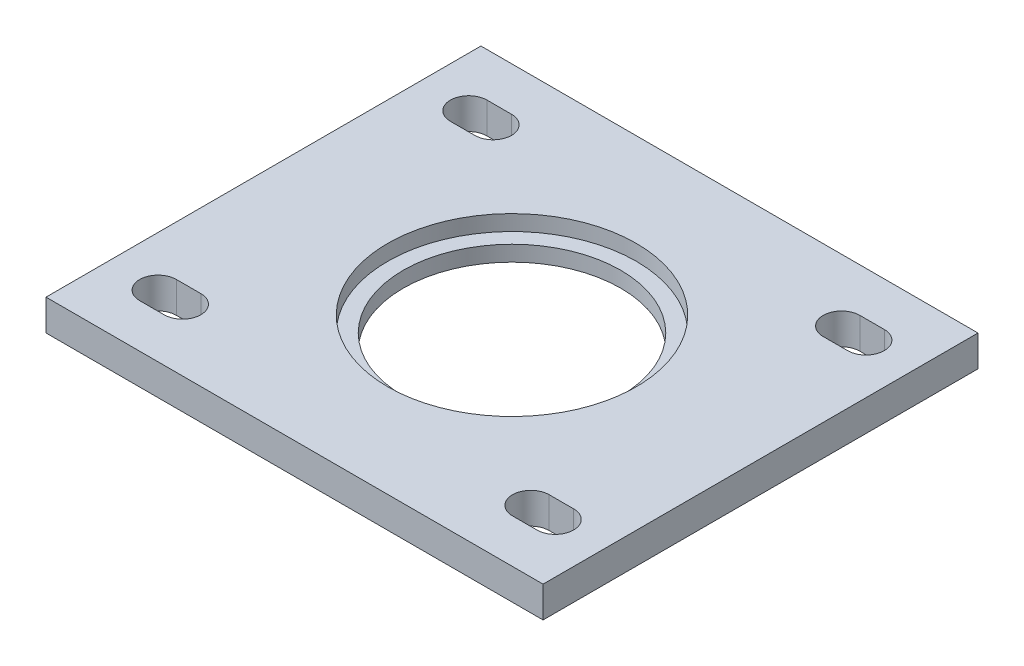
SolidWorks part; units mm, degrees
material "1023 Carbon Steel Sheet (SS)"
ref_plane "Front Plane" through (0, 0, 0) normal (0, 0, 1) x (1, 0, 0)
ref_plane "Top Plane" through (0, 0, 0) normal (0, 1, 0) x (1, 0, 0)
ref_plane "Right Plane" through (0, 0, 0) normal (1, 0, 0) x (0, 0, -1)
sketch "Sketch1" plane through (0, 0, 0) normal (0, 1, 0) x (1, 0, 0)
  line L1 (50.8, -44.45) -> (-50.8, -44.45)
  line L2 (50.8, -44.45) -> (50.8, 44.45)
  line L3 (50.8, 44.45) -> (-50.8, 44.45)
  line L4 (-50.8, -44.45) -> (-50.8, 44.45)
  line L5 (50.8, -44.45) -> (-50.8, 44.45) construction
  line L6 (50.8, 44.45) -> (-50.8, -44.45) construction
  circle A0 centre (0, 0) radius 25.4
  point P0 (0, 0)
  dimension "D3" = 50.8
  dimension "D1" = 88.9
  dimension "D2" = 101.6
extrude "Boss-Extrude1" add sketch "Sketch1" along normal blind 3.175
sketch "Sketch2" plane through (0, 3.175, 0) normal (0, 1, 0) x (1, 0, 0)
  line L0 (-40.6, 31.75) -> (-35.6, 31.75) construction
  line L1 (-40.6, 35.5) -> (-35.6, 35.5)
  line L2 (-40.6, 28) -> (-35.6, 28)
  line L3 (-38.1, 31.75) -> (-38.1, -31.75) construction
  line L4 (-40.6, -31.75) -> (-35.6, -31.75) construction
  line L5 (-40.6, -28) -> (-35.6, -28)
  line L6 (-40.6, -35.5) -> (-35.6, -35.5)
  line L7 (35.6, 31.75) -> (40.6, 31.75) construction
  line L8 (35.6, 35.5) -> (40.6, 35.5)
  line L9 (35.6, 28) -> (40.6, 28)
  line L10 (38.1, 31.75) -> (38.1, -31.75) construction
  line L11 (35.6, -31.75) -> (40.6, -31.75) construction
  line L12 (35.6, -28) -> (40.6, -28)
  line L13 (35.6, -35.5) -> (40.6, -35.5)
  line L14 (-38.1, -31.75) -> (38.1, -31.75) construction
  line L15 (-50.8, 44.45) -> (-50.8, -44.45) construction
  arc A0 (-40.6, 35.5) -> (-40.6, 28) centre (-40.6, 31.75) ccw
  arc A1 (-35.6, 28) -> (-35.6, 35.5) centre (-35.6, 31.75) ccw
  arc A2 (-40.6, -28) -> (-40.6, -35.5) centre (-40.6, -31.75) ccw
  arc A3 (-35.6, -35.5) -> (-35.6, -28) centre (-35.6, -31.75) ccw
  arc A4 (35.6, 35.5) -> (35.6, 28) centre (35.6, 31.75) ccw
  arc A5 (40.6, 28) -> (40.6, 35.5) centre (40.6, 31.75) ccw
  arc A6 (35.6, -28) -> (35.6, -35.5) centre (35.6, -31.75) ccw
  arc A7 (40.6, -35.5) -> (40.6, -28) centre (40.6, -31.75) ccw
  point P2 (-38.1, 31.75)
  point P11 (-38.1, -31.75)
  point P16 (0, -31.75)
  point P17 (-38.1, 0)
  point P21 (38.1, 31.75)
  point P30 (38.1, -31.75)
  point P35 (38.1, 0)
  dimension "D1" = 7.5
  dimension "D2" = 5
  dimension "D3" = 63.5
  dimension "D4" = 12.7
extrude "Cut-Extrude1" cut sketch "Sketch2" against normal through all
sketch "Sketch3" plane through (0, 3.175, 0) normal (0, 1, 0) x (1, 0, 0)
  line L0 (40.6, 35.5) -> (35.6, 35.5) construction
  line L1 (35.6, 28) -> (40.6, 28) construction
  line L2 (40.6, -28) -> (35.6, -28) construction
  line L3 (35.6, -35.5) -> (40.6, -35.5) construction
  line L4 (-50.8, 44.45) -> (-50.8, -44.45)
  line L5 (-50.8, -44.45) -> (50.8, -44.45)
  line L6 (50.8, -44.45) -> (50.8, 44.45)
  line L7 (50.8, 44.45) -> (-50.8, 44.45)
  line L8 (-50.8, 44.45) -> (-50.8, -44.45)
  line L9 (-50.8, -44.45) -> (50.8, -44.45)
  line L10 (50.8, -44.45) -> (50.8, 44.45)
  line L11 (50.8, 44.45) -> (-50.8, 44.45)
  line L12 (-35.6, -28) -> (-40.6, -28) construction
  line L13 (-40.6, -35.5) -> (-35.6, -35.5) construction
  line L14 (-35.6, 35.5) -> (-40.6, 35.5) construction
  line L15 (-40.6, 28) -> (-35.6, 28) construction
  line L16 (40.6, 35.5) -> (35.6, 35.5)
  line L17 (35.6, 28) -> (40.6, 28)
  line L18 (40.6, -28) -> (35.6, -28)
  line L19 (35.6, -35.5) -> (40.6, -35.5)
  line L20 (-35.6, -28) -> (-40.6, -28)
  line L21 (-40.6, -35.5) -> (-35.6, -35.5)
  line L22 (-35.6, 35.5) -> (-40.6, 35.5)
  line L23 (-40.6, 28) -> (-35.6, 28)
  arc A0 (40.6, 28) -> (40.6, 35.5) centre (40.6, 31.75) ccw construction
  arc A1 (35.6, 35.5) -> (35.6, 28) centre (35.6, 31.75) ccw construction
  arc A2 (40.6, -35.5) -> (40.6, -28) centre (40.6, -31.75) ccw construction
  arc A3 (35.6, -28) -> (35.6, -35.5) centre (35.6, -31.75) ccw construction
  arc A4 (-35.6, -35.5) -> (-35.6, -28) centre (-35.6, -31.75) ccw construction
  arc A5 (-40.6, -28) -> (-40.6, -35.5) centre (-40.6, -31.75) ccw construction
  arc A6 (-40.6, 35.5) -> (-40.6, 28) centre (-40.6, 31.75) ccw construction
  arc A7 (-35.6, 28) -> (-35.6, 35.5) centre (-35.6, 31.75) ccw construction
  circle A8 centre (0, 0) radius 25.4 construction
  arc A9 (40.6, 28) -> (40.6, 35.5) centre (40.6, 31.75) ccw
  arc A10 (35.6, 35.5) -> (35.6, 28) centre (35.6, 31.75) ccw
  arc A11 (40.6, -35.5) -> (40.6, -28) centre (40.6, -31.75) ccw
  arc A12 (35.6, -28) -> (35.6, -35.5) centre (35.6, -31.75) ccw
  arc A13 (-35.6, -35.5) -> (-35.6, -28) centre (-35.6, -31.75) ccw
  arc A14 (-40.6, -28) -> (-40.6, -35.5) centre (-40.6, -31.75) ccw
  arc A15 (-40.6, 35.5) -> (-40.6, 28) centre (-40.6, 31.75) ccw
  arc A16 (-35.6, 28) -> (-35.6, 35.5) centre (-35.6, 31.75) ccw
  circle A17 centre (0, 0) radius 25.4
  dimension "D1" = 0
extrude "Boss-Extrude2" add sketch "Sketch3" along normal blind 3.175
sketch "Sketch5" plane through (0, 0, 0) normal (0, -1, 0) x (1, 0, 0)
  circle A0 centre (0, 0) radius 22.225
  circle A1 centre (0, 0) radius 31.75
  dimension "D1" = 44.45
  dimension "D2" = 63.5
extrude "Boss-Extrude3" add sketch "Sketch5" against normal blind 3.175
